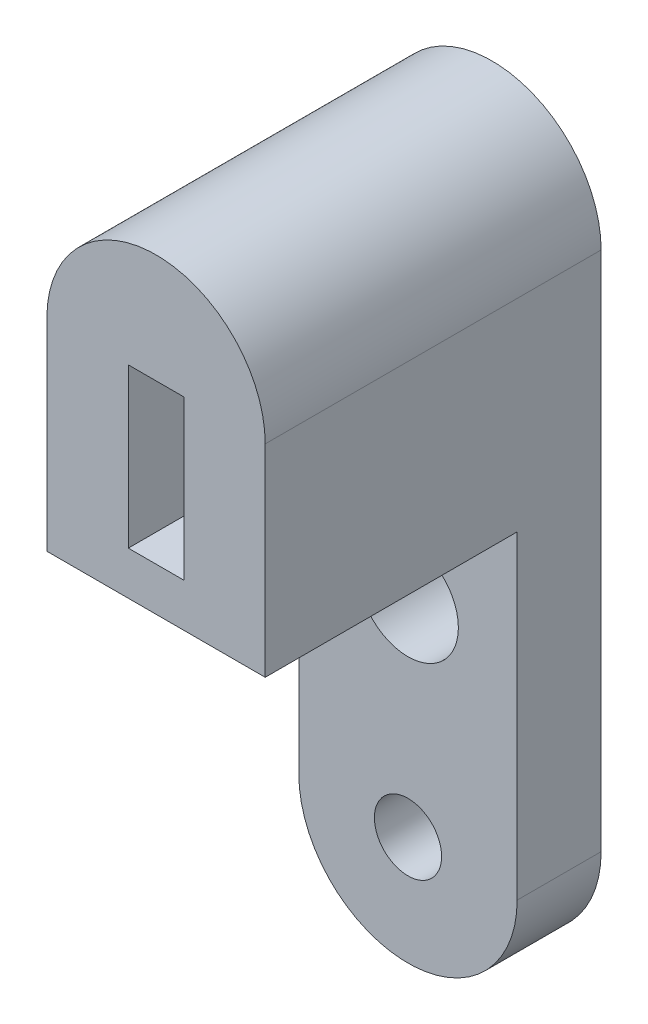
SolidWorks part; units mm, degrees
ref_plane "Front Plane" through (0, 0, 0) normal (0, 0, 1) x (1, 0, 0)
ref_plane "Top Plane" through (0, 0, 0) normal (0, 1, 0) x (1, 0, 0)
ref_plane "Right Plane" through (0, 0, 0) normal (1, 0, 0) x (0, 0, -1)
sketch "Sketch1" plane through (0, 0, 0) normal (0, 0, 1) x (1, 0, 0)
  line L0 (0, -17.7121) -> (0, 13.3129) construction
  line L3 (-1.65, 3.8629) -> (1.65, 3.8629)
  line L4 (-1.65, 3.8629) -> (-1.65, 13.3129)
  line L5 (-1.65, 13.3129) -> (1.65, 13.3129)
  line L6 (1.65, 3.8629) -> (1.65, 13.3129)
  line L7 (-1.65, 3.8629) -> (1.65, 13.3129) construction
  line L8 (-1.65, 13.3129) -> (1.65, 3.8629) construction
  line L9 (-6.5, -17.7121) -> (-6.5, 13.3129)
  line L10 (6.5, -17.7121) -> (6.5, 13.3129)
  line L11 (-6.5, 1.2763) -> (6.5, 1.2763)
  circle A1 centre (0, -5.4121) radius 3
  circle A2 centre (0, -17.7121) radius 2
  arc A5 (-6.5, -17.7121) -> (6.5, -17.7121) centre (0, -17.7121) ccw
  arc A6 (6.5, 13.3129) -> (-6.5, 13.3129) centre (0, 13.3129) ccw
  point P0 (0, 8.5879)
  point P1 (0, -2.1996)
  dimension "D1" = 4
  dimension "D2" = 6
  dimension "D3" = 9.45
  dimension "D5" = 7.3
  dimension "D8" = 14
  dimension "D4" = 3.3
  dimension "D7" = 13
extrude "Boss-Extrude1" add sketch "Sketch1" along normal blind 5 contours L9 A5 L10 L11 A1 A2 | L10 A6 L9 L11 L6 L3 L4 L5 region at (0, -11.0566, 0) region at (-6.2736, 7.2946, 0)
extrude "Boss-Extrude2" add sketch "Sketch1<4>" along normal blind 20 contours L10 A6 L9 L11 L6 L3 L4 L5 region at (-6.2736, 7.2946, 0)
sketch "Sketch1<4>" plane through (0, 0, 0) normal (0, 0, 1) x (1, 0, 0) same geometry as "Sketch1"
ref_plane "Plane1" through (0, 0, 10) normal (0, 0, -1) x (-1, 0, 0)
ref_plane "Plane2" through (0, 8.5879, 0) normal (0, -1, 0) x (-1, 0, 0)
ref_axis "Axis1" through (5.5, 8.5879, 10) along (-1, 0, 0)
sketch "Sketch2" plane through (-6.5, 0, 0) normal (-1, 0, 0) x (0, 0, 1)
  line L1 (14.766, 8.5879) -> (12.383, 12.7154)
  line L2 (12.383, 12.7154) -> (7.617, 12.7154)
  line L3 (7.617, 12.7154) -> (5.234, 8.5879)
  line L4 (5.234, 8.5879) -> (7.617, 4.4604)
  line L5 (7.617, 4.4604) -> (12.383, 4.4604)
  line L6 (12.383, 4.4604) -> (14.766, 8.5879)
  line L7 (-1.815, 8.5879) -> (1.815, 8.5879) construction
  circle A0 centre (10, 8.5879) radius 4.1275 construction
  circle A1 centre (10, 8.5879) radius 2.3813
  dimension "D2" = 4.7625
  dimension "D1" = 8.255
extrude "Cut-Extrude1" cut sketch "Sketch2" against normal blind 3.175 contours L6 L1 L2 L3 L4 L5
extrude "Cut-Extrude2" cut sketch "Sketch2<3>" against normal up to next contours A1 region at (-6.5, 8.5879, 10)
sketch "Sketch2<3>" plane through (-6.5, 0, 0) normal (-1, 0, 0) x (0, 0, 1) same geometry as "Sketch2"
